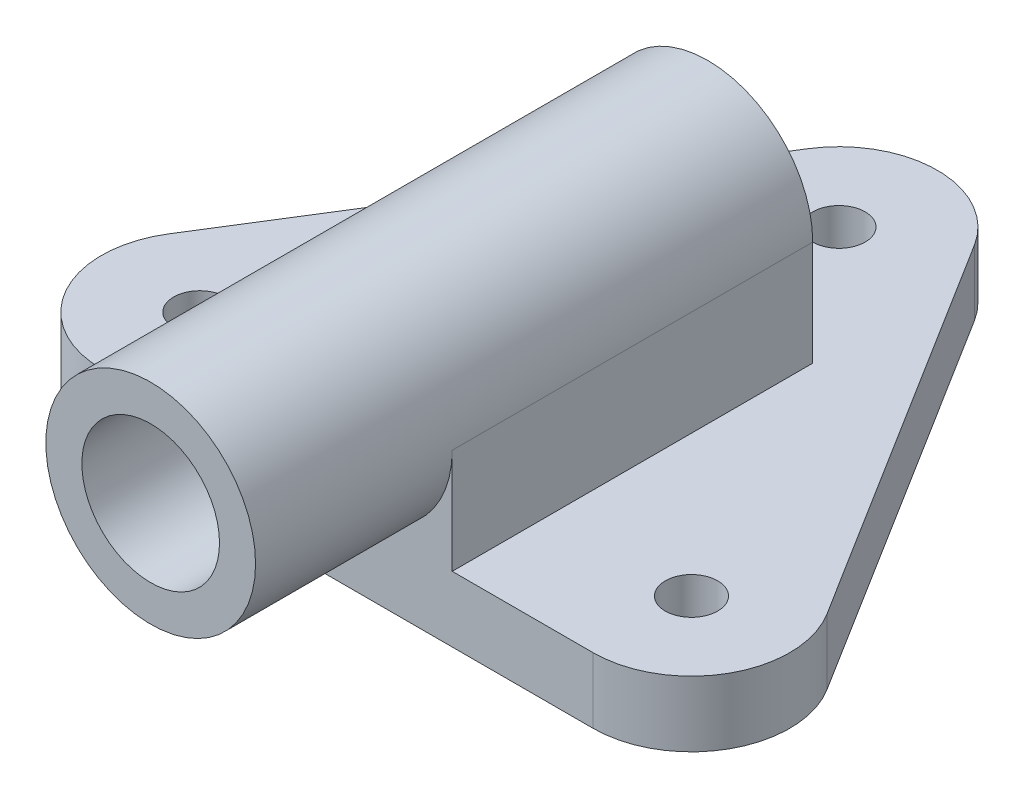
SolidWorks part; units mm, degrees
ref_plane "Front Plane" through (0, 0, 0) normal (0, 0, 1) x (1, 0, 0)
ref_plane "Top Plane" through (0, 0, 0) normal (0, 1, 0) x (1, 0, 0)
ref_plane "Right Plane" through (0, 0, 0) normal (1, 0, 0) x (0, 0, -1)
sketch "Sketch1" plane through (0, 0, 0) normal (0, 1, 0) x (1, 0, 0)
  line L0 (0, 0) -> (-37.5, -60) construction
  line L1 (-37.5, -60) -> (37.5, -60) construction
  line L2 (37.5, -60) -> (0, 0) construction
  line L4 (0, 0) -> (-37.5, -60) construction
  line L5 (-37.5, -60) -> (0, 0) construction
  line L6 (37.5, -60) -> (0, 0) construction
  line L7 (-12.72, 7.95) -> (-50.22, -52.05)
  line L8 (-37.5, -75) -> (37.5, -75)
  line L9 (50.22, -52.05) -> (12.72, 7.95)
  line L13 (0, 28.3019) -> (-64.5637, -75) construction
  line L14 (64.5637, -75) -> (0, 28.3019) construction
  line L15 (-64.5637, -75) -> (64.5637, -75) construction
  line L17 (0, -28.3019) -> (0, 0) construction
  circle A0 centre (0, 0) radius 15
  circle A3 centre (0, 0) radius 4
  circle A4 centre (37.5, -60) radius 15
  circle A5 centre (37.5, -60) radius 4
  circle A6 centre (-37.5, -60) radius 15
  circle A7 centre (-37.5, -60) radius 4
  point P10 (-37.5, -24.2748)
  point P12 (0, 0)
  point P13 (0, 0)
  point P14 (0, -19.1265)
  point P15 (0, 0)
  point P16 (0, 0)
  point P18 (0, -60)
  dimension "D1" = 8
  dimension "D2" = 30
  dimension "D3" = 8
  dimension "D4" = 30
  dimension "D5" = 8
  dimension "D6" = 30
  dimension "D7" = 75
  dimension "D8" = 60
  dimension "D9" = 15
extrude "Boss-Extrude1" add sketch "Sketch1" along normal blind 10 contours A6 L8 A4 L9 A0 L7 | A6 A7 | A0 A3 | A4 A5 region at (0, 0, 40.4275) region at (0, 0, -14.5757) region at (-33.4817, 0, 45.9891) region at (51.5109, 0, 55.9817)
sketch "Sketch3" plane through (0, 0, 75) normal (0, 0, 1) x (1, 0, 0)
  line L0 (-37.5, 10) -> (37.5, 10) construction
  circle A0 centre (0, 26) radius 10.5
  circle A1 centre (0, 26) radius 16
  dimension "D1" = 21
  dimension "D2" = 32
extrude "Boss-Extrude2" add sketch "Sketch3" along normal blind 30 and the other way blind 55 separate body
sketch "Sketch4" plane through (0, 0, 75) normal (0, 0, 1) x (1, 0, 0)
  line L0 (-16, 26) -> (-16, 10)
  line L1 (-37.5, 10) -> (37.5, 10) construction
  line L2 (-16, 10) -> (16, 10)
  line L3 (16, 10) -> (16, 26)
  circle A0 centre (0, 26) radius 16 construction
  circle A2 centre (0, 26) radius 16
  arc A3 (-16, 26) -> (16, 26) centre (0, 26) ccw
  line M7 (37.5, 10) -> (-37.5, 10)
  dimension "D1" = 0
extrude "Boss-Extrude3" add sketch "Sketch4" against normal up to surface (55 mm away) contours A3 L3 M7 | A3 L0 L2 region at (-12.4261, 13.5739, 75) region at (12.4261, 13.5739, 75) up to face at (10.5, 26, 20)
